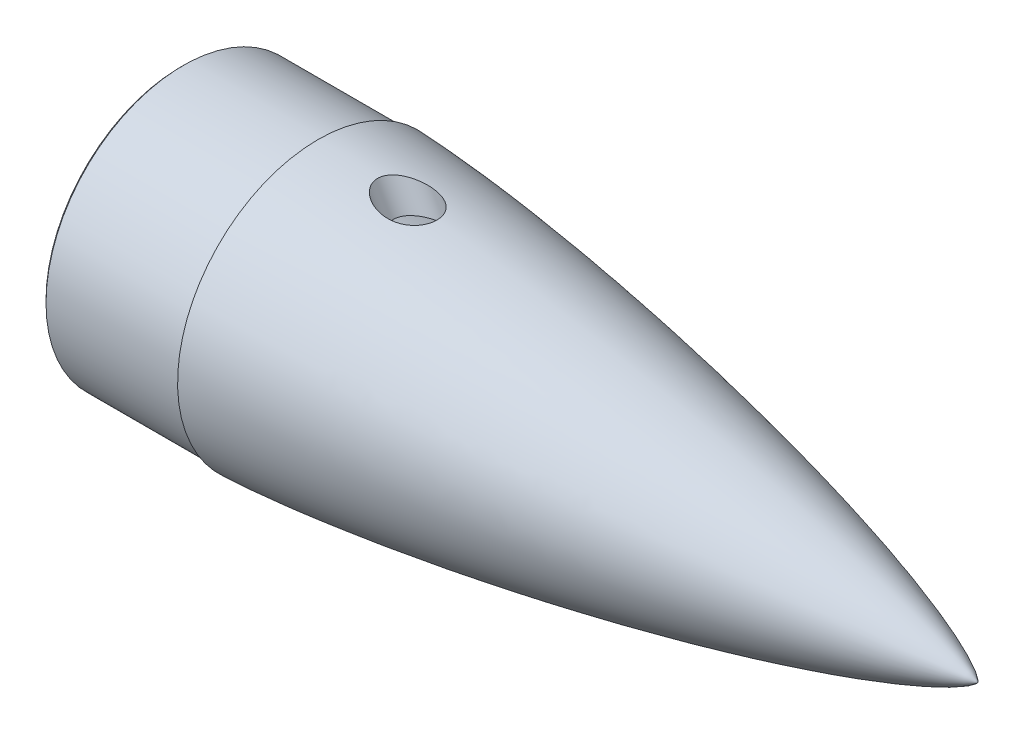
SolidWorks part; units mm, degrees
material "Plain Carbon Steel"
ref_plane "Front Plane" through (0, 0, 0) normal (0, 0, 1) x (1, 0, 0)
ref_plane "Top Plane" through (0, 0, 0) normal (0, 1, 0) x (1, 0, 0)
ref_plane "Right Plane" through (0, 0, 0) normal (1, 0, 0) x (0, 0, -1)
ref_axis "Axis1" through (433.6458, 0, 0) along (-1, 0, 0)
sketch "Sketch10" plane through (0, 0, 0) normal (0, 0, 1) x (1, 0, 0)
  line L1 (-1.0327, 0) -> (486.9547, 0) construction
  line L2 (11.1125, 81.9998) -> (11.1125, 67.4998)
  line L3 (11.1125, 81.9998) -> (-84.6045, 81.9998)
  line L4 (408.9673, 0) -> (368.9673, 0)
  line L5 (-84.6045, 81.9998) -> (-84.6045, 84.9998)
  line L6 (-84.6045, 84.9998) -> (0.3953, 84.9998)
  line L7 (0.3953, 84.9998) -> (0.3953, 86.9998)
  line L8 (11.1125, 67.4998) -> (129.3045, 67.4998)
  line L9 (433.6458, 0) -> (-109.2831, 0) construction
  spline S0 degree 4 poles (408.9673, 0) (408.9649, 0.0135) (408.958, 0.0399) (408.9365, 0.0905) (408.8922, 0.1741) (408.8263, 0.2756) (408.7217, 0.4158) (408.5611, 0.6051) (408.3056, 0.8724) (407.8697, 1.2753) (407.121, 1.8851) (405.8038, 2.8259) (403.4624, 4.2872) (399.3253, 6.5318) (392.4811, 9.7589) (380.6621, 14.628) (363.6372, 20.7117) (342.2152, 27.4765) (317.4285, 34.4976) (291.8793, 41.1048) (266.2105, 47.229) (240.4455, 52.9334) (214.5989, 58.2554) (188.6809, 63.2176) (165.9462, 67.2533) (146.422, 70.4938) (130.1279, 73.0449) (117.0786, 74.9942) (104.0155, 76.8485) (92.5733, 78.3845) (82.7571, 79.6356) (74.5713, 80.6322) (68.0193, 81.4008) (61.4637, 82.1394) (54.9047, 82.8464) (48.3422, 83.5199) (41.7761, 84.1578) (36.0275, 84.6822) (31.0979, 85.1052) (26.9883, 85.4387) (23.6997, 85.6932) (20.0858, 85.9584) (16.7199, 86.189) (13.6021, 86.387) (10.7327, 86.5546) (8.4366, 86.6787) (6.14, 86.7922) (4.1299, 86.8793) (2.4065, 86.9446) (1.2573, 86.979) (0.6827, 86.9949) (0.3953, 86.9998) knots 0 0 0 0 0 0.00013 0.00026 0.00052 0.0009 0.00128 0.001925 0.002882 0.004418 0.006927 0.011111 0.018279 0.030673 0.051704 0.083102 0.139909 0.202703 0.265496 0.32829 0.391083 0.453877 0.516671 0.579464 0.642258 0.673655 0.705051 0.736448 0.767845 0.799242 0.81494 0.830639 0.846337 0.862036 0.877734 0.893432 0.909131 0.924829 0.932678 0.940527 0.948377 0.956226 0.967169 0.972641 0.978113 0.983585 0.989056 0.994528 0.997264 1 1 1 1 1 construction
  spline S1 degree 4 poles (408.9673, 0) (408.9649, 0.0135) (408.958, 0.0399) (408.9365, 0.0905) (408.8922, 0.1741) (408.8263, 0.2756) (408.7217, 0.4158) (408.5611, 0.6051) (408.3056, 0.8724) (407.8697, 1.2753) (407.121, 1.8851) (405.8038, 2.8259) (403.4624, 4.2872) (399.3253, 6.5318) (392.4811, 9.7589) (380.6621, 14.628) (363.6372, 20.7117) (342.2152, 27.4765) (317.4285, 34.4976) (291.8793, 41.1048) (266.2105, 47.229) (240.4455, 52.9334) (214.5989, 58.2554) (188.6809, 63.2176) (165.9462, 67.2533) (146.422, 70.4938) (130.1279, 73.0449) (117.0786, 74.9942) (104.0155, 76.8485) (92.5733, 78.3845) (82.7571, 79.6356) (74.5713, 80.6322) (68.0193, 81.4008) (61.4637, 82.1394) (54.9047, 82.8464) (48.3422, 83.5199) (41.7761, 84.1578) (36.0275, 84.6822) (31.0979, 85.1052) (26.9883, 85.4387) (23.6997, 85.6932) (20.0858, 85.9584) (16.7199, 86.189) (13.6021, 86.387) (10.7327, 86.5546) (8.4366, 86.6787) (6.14, 86.7922) (4.1299, 86.8793) (2.4065, 86.9446) (1.2573, 86.979) (0.6827, 86.9949) (0.3953, 86.9998) knots 0 0 0 0 0 0.00013 0.00026 0.00052 0.0009 0.00128 0.001925 0.002882 0.004418 0.006927 0.011111 0.018279 0.030673 0.051704 0.083102 0.139909 0.202703 0.265496 0.32829 0.391083 0.453877 0.516671 0.579464 0.642258 0.673655 0.705051 0.736448 0.767845 0.799242 0.81494 0.830639 0.846337 0.862036 0.877734 0.893432 0.909131 0.924829 0.932678 0.940527 0.948377 0.956226 0.967169 0.972641 0.978113 0.983585 0.989056 0.994528 0.997264 1 1 1 1 1
  spline S2 degree 4 poles (368.9673, 0) (368.9653, 0.0123) (368.9594, 0.0365) (368.9406, 0.083) (368.9023, 0.1587) (368.8455, 0.2503) (368.7557, 0.3766) (368.6167, 0.5484) (368.3929, 0.7936) (368.0087, 1.1649) (367.3447, 1.7299) (366.1761, 2.6016) (364.0928, 3.96) (360.426, 6.0407) (354.4022, 9.0183) (344.043, 13.5077) (329.152, 19.1285) (310.4252, 25.3986) (288.7413, 31.9337) (266.3785, 38.1061) (243.9014, 43.8469) (221.332, 49.212) (198.684, 54.2345) (175.9669, 58.9343) (156.0346, 62.7717) (138.9133, 65.8645) (124.6221, 68.3077) (113.1754, 70.1797) (101.7151, 71.9664) (91.6754, 73.4517) (83.0615, 74.6659) (75.8775, 75.6363) (70.1269, 76.3867) (64.3728, 77.1101) (58.6152, 77.8049) (52.854, 78.4695) (47.0892, 79.1019) (42.0417, 79.6247) (37.7129, 80.0488) (34.1039, 80.385) (31.2157, 80.6428) (28.0648, 80.911) (24.6507, 81.1843) (21.4654, 81.4195) (18.5093, 81.6177) (16.0448, 81.767) (14.3191, 81.8612) (12.8395, 81.9336) (11.8527, 81.9739) (11.3593, 81.993) (11.1125, 81.9998) knots 0 0 0 0 0 0.000135 0.00027 0.00054 0.00092 0.001299 0.001947 0.002931 0.004512 0.007081 0.01138 0.018708 0.031424 0.052705 0.084103 0.14091 0.203703 0.266497 0.329291 0.392084 0.454878 0.517672 0.580465 0.643259 0.674656 0.706052 0.737449 0.768846 0.800243 0.815941 0.831639 0.847338 0.863036 0.878735 0.894433 0.910132 0.92583 0.933679 0.941528 0.949378 0.957227 0.96792 0.978613 0.98396 0.989307 0.994653 0.997327 1 1 1 1 1 construction
  spline S3 degree 4 poles (368.9673, 0) (368.9653, 0.0123) (368.9594, 0.0365) (368.9406, 0.083) (368.9023, 0.1587) (368.8455, 0.2503) (368.7557, 0.3766) (368.6167, 0.5484) (368.3929, 0.7936) (368.0087, 1.1649) (367.3447, 1.7299) (366.1761, 2.6016) (364.0928, 3.96) (360.426, 6.0407) (354.4022, 9.0183) (344.043, 13.5077) (329.152, 19.1285) (310.4252, 25.3986) (288.7413, 31.9337) (266.3785, 38.1061) (243.9014, 43.8469) (221.332, 49.212) (198.684, 54.2345) (175.9669, 58.9343) (156.0346, 62.7717) (141.5091, 65.3956) (132.6794, 66.9245) (129.5628, 67.4559) (129.3045, 67.4998) knots 0 0 0 0 0 0.000135 0.00027 0.00054 0.00092 0.001299 0.001947 0.002931 0.004512 0.007081 0.01138 0.018708 0.031424 0.052705 0.084103 0.14091 0.203703 0.266497 0.329291 0.392084 0.454878 0.517672 0.580465 0.643259 0.674656 0.677492 0.677492 0.677492 0.677492 0.677492
  dimension "D1" = 86.9998
  dimension "D2" = 3
  dimension "D3" = 410
  dimension "D4" = 84.9998
  dimension "D5" = 370
  dimension "D6" = 84.9998
  dimension "D7" = 19.5
  dimension "D8" = 118.192
revolve "Revolve1" add sketch "Sketch10" angle 360 about axis through (433.6458, 0, 0) along (-1, 0, 0)
chamfer "Chamfer1" distance 1.5 angle 45 1 edges at (-84.6045, 0, -84.9998)
ref_plane "Plane2" through (11.1125, 0, 0) normal (-1, 0, 0) x (0, 0, 1)
sketch "Sketch12" plane through (11.1125, 0, 0) normal (-1, 0, 0) x (0, 0, 1)
  circle A4 centre (-73.1248, 0) radius 4
  circle A5 centre (-36.5624, 63.328) radius 4
  circle A6 centre (36.5624, 63.328) radius 4
  circle A7 centre (73.1248, 0) radius 4
  circle A8 centre (36.5624, -63.328) radius 4
  circle A9 centre (-36.5624, -63.328) radius 4
  point P17 (-50.2998, -44.6412)
  point P25 (0, 0)
  dimension "D1" = 6
hole_wizard "Tap Drill for #1 Helicoil1" positions "Sketch17" profile "Sketch18" hole size "#1-64" standard "ANSI Inch"
sketch "Sketch17" plane through (11.1125, 0, 0) normal (-1, 0, 0) x (0, 0, 1)
  point P0 (-36.5624, 63.328)
sketch "Sketch18" plane through (11.1125, 63.328, -36.5624) normal (0, 1, 0) x (0, 0, 1)
  line L0 (0, 0) -> (0, 9.525)
  line L1 (0, 9.525) -> (3.3782, 9.525)
  line L2 (3.3782, 9.525) -> (3.3782, 0)
  line L5 (3.3782, 0) -> (0, 0)
  line L10 (0, 9.525) -> (-3.3782, 9.525) construction
  line L11 (0, -6.35) -> (0, 107.95) construction
  dimension "Hole Dia." = 6.7564
  dimension "Hole Depth" = 9.525
  dimension "Drill Angle" = 180
pattern_circular "CirPattern1" count 6 over 360 about axis through (11.1125, 0, 0) along (1, 0, 0) of "Tap Drill for #1 Helicoil1"
ref_plane "Plane3" through (0, 60, 0) normal (0, 1, 0) x (1, 0, 0)
sketch "Sketch20" plane through (0, 60, 0) normal (0, 1, 0) x (1, 0, 0)
  line L0 (433.6458, 0) -> (-109.2831, 0) construction
  line L1 (24.7702, 25) -> (64.7702, 25)
  line L2 (24.7702, 25) -> (24.7702, -15)
  line L3 (24.7702, -15) -> (64.7702, -15)
  line L4 (64.7702, 25) -> (64.7702, -15)
  line L5 (24.7702, 25) -> (64.7702, -15) construction
  line L6 (24.7702, -15) -> (64.7702, 25) construction
  point P4 (44.7702, 5)
  dimension "D1" = 40
  dimension "D2" = 15
  dimension "D3" = 40
extrude "Cut-Extrude3" [suppressed] cut sketch "Sketch20" along normal blind 12
sketch "Sketch22" plane through (0, 60, 0) normal (0, 1, 0) x (1, 0, 0)
  circle A0 centre (32, 6) radius 7.5
  dimension "D1" = 15
extrude "Cut-Extrude4" [suppressed] cut sketch "Sketch22" along normal through all
sketch "Sketch24" plane through (0, 60, 0) normal (0, 1, 0) x (1, 0, 0)
  line L0 (38.1988, 66.2764) -> (38.1988, 16.8548) construction
ref_plane "Plane4" through (-16.4311, 28.4594, 0) normal (-0.5, 0.866, 0) x (0, 0, 1)
sketch "Sketch26" plane through (-16.4311, 28.4594, 0) normal (-0.5, 0.866, 0) x (0, 0, 1)
  circle A0 centre (0, 89.5256) radius 15
extrude "Cut-Extrude5" cut sketch "Sketch26" against normal blind 50
extrude "Cut-Extrude6" cut sketch "Sketch26<2>" along normal blind 50
sketch "Sketch26<2>" plane through (-16.4311, 28.4594, 0) normal (-0.5, 0.866, 0) x (0, 0, 1) same geometry as "Sketch26"
equation "\"TubeDiameter\" = 6.250in"
